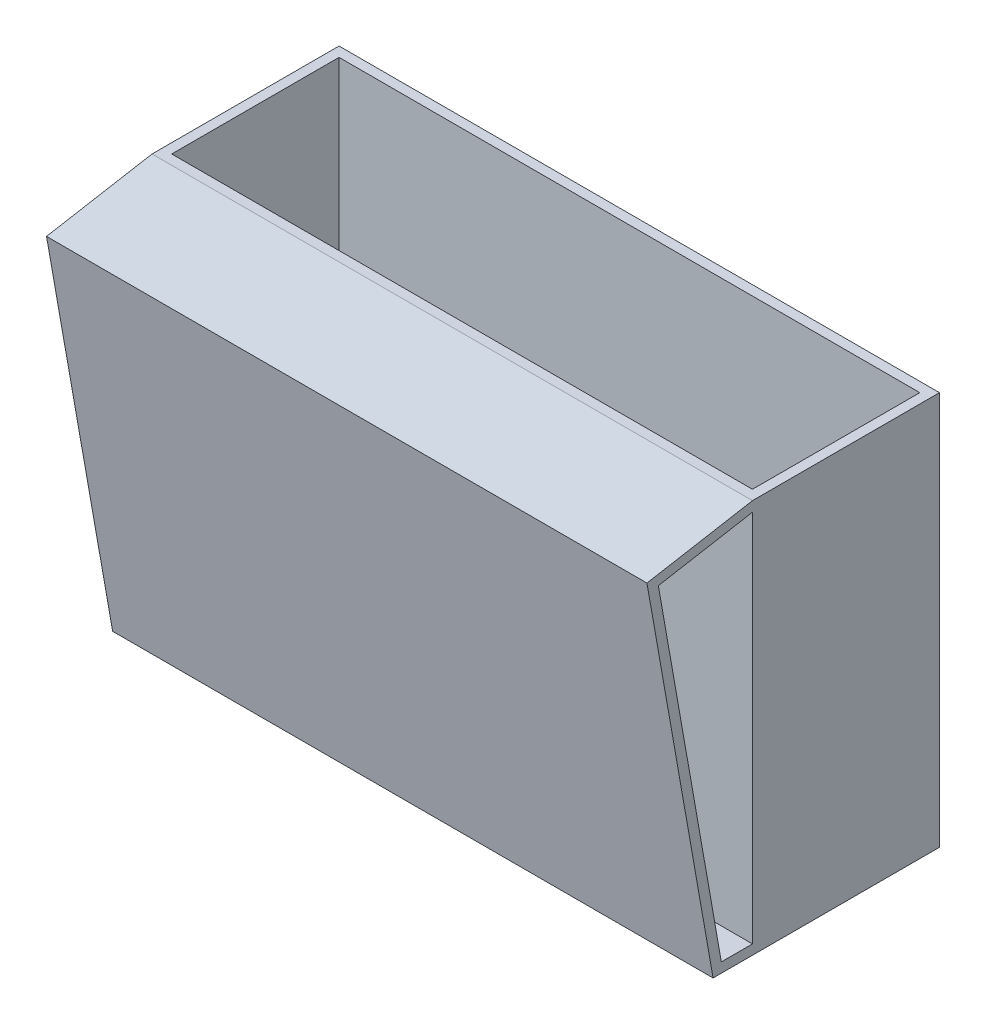
SolidWorks part; units mm, degrees
ref_plane "Front Plane" through (0, 0, 0) normal (0, 0, 1) x (1, 0, 0)
ref_plane "Top Plane" through (0, 0, 0) normal (0, 1, 0) x (1, 0, 0)
ref_plane "Right Plane" through (0, 0, 0) normal (1, 0, 0) x (0, 0, -1)
sketch "Sketch1" plane through (0, 0, 0) normal (0, 1, 0) x (1, 0, 0)
  line L0 (-14.75, 4.25) -> (-15.25, 4.25) construction
  line L1 (-14.75, 4.25) -> (14.75, 4.25)
  line L2 (-14.75, 4.25) -> (-14.75, -4.25)
  line L3 (-14.75, -4.25) -> (14.75, -4.25)
  line L4 (14.75, 4.25) -> (14.75, -4.25)
  line L5 (-14.75, 4.25) -> (14.75, -4.25) construction
  line L6 (-14.75, -4.25) -> (14.75, 4.25) construction
  line L7 (15.25, 4.75) -> (-15.25, 4.75)
  line L8 (15.25, 4.75) -> (15.25, -4.75)
  line L9 (15.25, -4.75) -> (-15.25, -4.75)
  line L10 (-15.25, 4.75) -> (-15.25, -4.75)
  line L11 (15.25, 4.75) -> (-15.25, -4.75) construction
  line L12 (15.25, -4.75) -> (-15.25, 4.75) construction
  line L13 (-14.75, 4.25) -> (-14.75, 4.75) construction
  line L17 (-15.25, -4.75) -> (15.25, -4.75)
  point P0 (0, 0)
  point P6 (0, 0)
  dimension "D1" = 29.5
  dimension "D2" = 8.5
  dimension "D3" = 0.5
extrude "Boss-Extrude1" add sketch "Sketch1" along normal blind 20 contours L9 | L7 L10 L9 L8 L1 L4 L3 L2 region at (14.9305, 0, 0)
sketch "Sketch2" plane through (-15.25, 0, 0) normal (-1, 0, 0) x (0, 0, 1)
  line L0 (4.75, 0) -> (6.75, 0)
  line L1 (6.75, 0) -> (10.1099, 19.0549)
  line L2 (10.1099, 19.0549) -> (4.75, 20)
  line L3 (6.75, 0) -> (6.75, 19.6473) construction
  line L4 (4.75, 20) -> (4.75, 0)
  line L5 (9.5307, 18.6493) -> (5.25, 19.4041)
  line L6 (5.25, 19.4041) -> (5.25, 0.5)
  line L7 (5.25, 0.5) -> (6.3305, 0.5)
  line L8 (6.3305, 0.5) -> (9.5307, 18.6493)
  line L9 (5.25, 19.4041) -> (4.75, 19.4923)
  line L10 (5.25, 0.5) -> (4.75, 0.5)
  line M6 (4.75, 0) -> (4.75, 20)
  dimension "D1" = 10
  dimension "D2" = 2
  dimension "D3" = 0.5
extrude "Boss-Extrude2" add sketch "Sketch2" against normal up to surface (30.5 mm away) contours L0 L3 L8 L7 L10 M6 | L3 L1 L2 L5 L8 | L5 L3 L2 L4 L9 region at (-15.25, 0.25, 4.7851) region at (-15.25, 11.4761, 8.2897) region at (-15.25, 19.5698, 5.75) up to face at (15.25, 10, 0)
